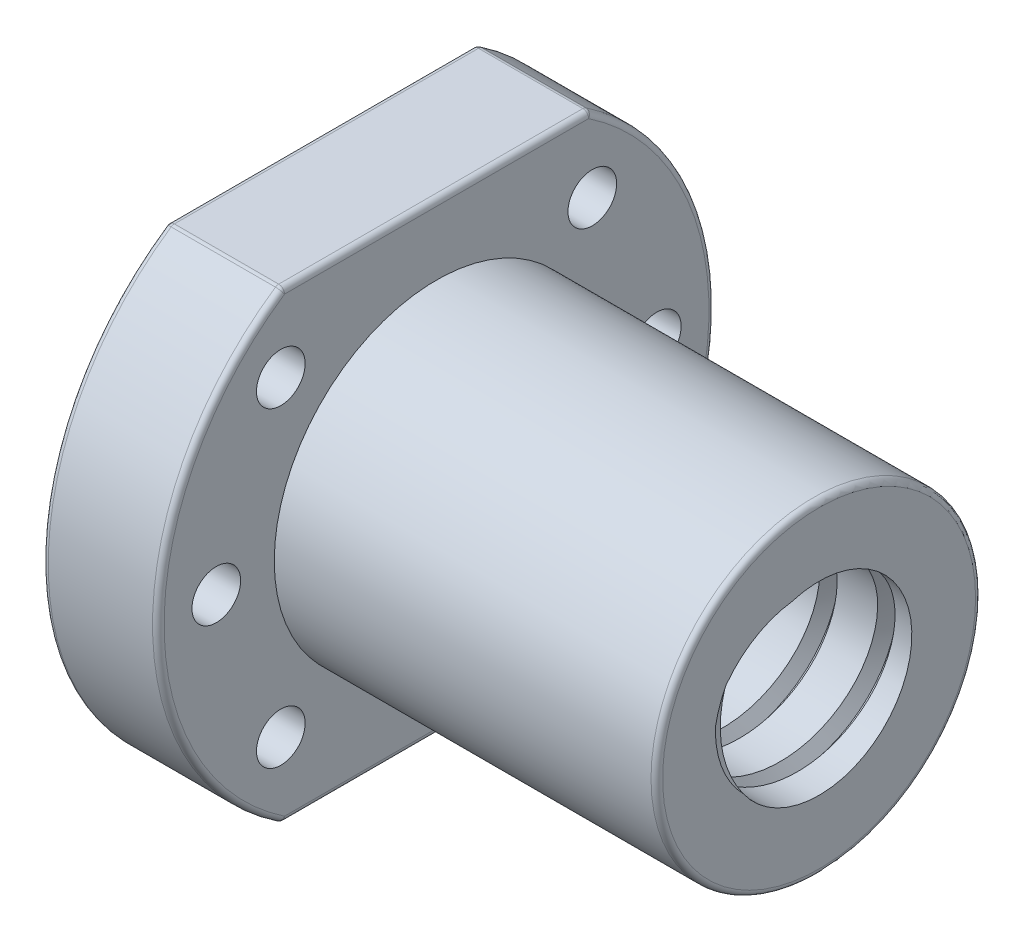
SolidWorks part; units mm, degrees
material "AISI 1015 Acero estirado en frío (SS)"
ref_plane "Alzado" through (0, 0, 0) normal (0, 0, 1) x (1, 0, 0)
ref_plane "Planta" through (0, 0, 0) normal (0, 1, 0) x (1, 0, 0)
ref_plane "Vista lateral" through (0, 0, 0) normal (1, 0, 0) x (0, 0, -1)
sketch "Croquis1" plane through (0, 0, 0) normal (1, 0, 0) x (0, 0, -1)
  circle A0 centre (0, 0) radius 14
  dimension "D1" = 28
extrude "Saliente-Extruir1" add sketch "Croquis1" along normal blind 33
sketch "Croquis2" plane through (0, 0, 0) normal (1, 0, 0) x (0, 0, -1)
  circle A0 centre (0, 0) radius 24
  dimension "D1" = 48
extrude "Saliente-Extruir2" add sketch "Croquis2" against normal blind 10
sketch "Croquis3" plane through (0, 0, 0) normal (1, 0, 0) x (0, 0, -1)
  circle A0 centre (0, 0) radius 8
  dimension "D1" = 16
extrude "Cortar-Extruir1" cut sketch "Croquis3" against normal through all both and the other way through all
ref_plane "Plano1" through (-10, 0, 0) normal (1, 0, 0) x (0, 0, -1)
sketch "Croquis4" plane through (-10, 0, 0) normal (1, 0, 0) x (0, 0, -1)
  line L0 (0, 20) -> (0, 0) construction
  line L1 (0, 0) -> (0, -20) construction
  line L2 (13.2665, 20) -> (-13.2665, 20)
  line L3 (-13.2665, 20) -> (-13.2665, 28)
  line L4 (-13.2665, 28) -> (13.2665, 28)
  line L5 (13.2665, 28) -> (13.2665, 20)
  line L6 (0, -20) -> (-13.2665, -20)
  line L7 (-13.2665, -20) -> (-13.2665, -28)
  line L8 (-13.2665, -28) -> (13.2665, -28)
  line L9 (13.2665, -28) -> (13.2665, -20)
  line L10 (13.2665, -20) -> (0, -20)
  circle A0 centre (0, 0) radius 24 construction
  dimension "D1" = 20
  dimension "D2" = 20
extrude "Cortar-Extruir2" cut sketch "Croquis4" along normal blind 10
fillet "Redondeo1" radius 0.5 1 edges at (33, 0, -14)
fillet "Redondeo2" radius 0.5 11 edges at (-10, 20, 0) (0, 20, 0) (-10, -20, 0) (0, -20, 0) (-5, -20, 13.2665) (-5, -20, -13.2665) (-5, 20, -13.2665) (-10, 0, -24) (0, 0, -24) (-10, 0, 24) (0, 0, 24)
fillet "Redondeo3" radius 0.5 3 edges at (-0.1977, 19.8982, 13.2358) (-9.8023, 19.8982, 13.2358) (-5, 20, 13.2665)
sketch "Croquis6" plane through (-10, 0, 0) normal (1, 0, 0) x (0, 0, -1)
  line L0 (0, 25.105) -> (0, -25.1968) construction
  line L1 (19, 0) -> (-19, 0) construction
  line L2 (13.435, 13.435) -> (0, 0) construction
  line L3 (0, 0) -> (13.435, -13.435) construction
  line L4 (-13.435, 13.435) -> (0, 0) construction
  line L5 (0, 0) -> (-13.435, -13.435) construction
  circle A1 centre (13.435, 13.435) radius 2.1
  circle A2 centre (-13.435, 13.435) radius 2.1
  circle A3 centre (-13.435, -13.435) radius 2.1
  circle A4 centre (13.435, -13.435) radius 2.1
  circle A5 centre (19, 0) radius 2.1
  circle A6 centre (-19, 0) radius 2.1
  dimension "D6" = 4.2
  dimension "D7" = 4.2
  dimension "D8" = 4.2
  dimension "D9" = 4.2
  dimension "D10" = 4.2
  dimension "D11" = 4.2
  dimension "D2" = 45
  dimension "D3" = 45
  dimension "D4" = 45
  dimension "D5" = 45
extrude "Cortar-Extruir3" cut sketch "Croquis6" along normal blind 10
thread "Rosca1" pitch 2 method cut profile "Perfil de rosca1" start angle 1, offset 11, length 55, pitch 5, diameter 16
ref_plane "Plano2" through (44, 0.1396, 7.9988) normal (0, -0.9998, 0.0175) x (0, 0.0175, 0.9998)
sketch "Perfil de rosca1" plane through (44, 0.1396, 7.9988) normal (0, -0.9998, 0.0175) x (0, 0.0175, 0.9998)
  line L0 (0, 0) -> (0, 2) construction
  line L1 (0, 0) -> (1.0825, 0.625)
  line L2 (1.0825, 0.625) -> (1.0825, 0.875)
  line L3 (1.0825, 0.875) -> (0, 1.5)
  line L4 (1.0825, 0.75) -> (0, 0.75) construction
  line L11 (0, 0) -> (0, 1.5)
  point P2 (0, 0)
  dimension "Pitch" = 2
  dimension "Profile_Angle" = 60
  dimension "Profile_Land" = 0.25
  dimension "Profile_Height" = 1.0825
